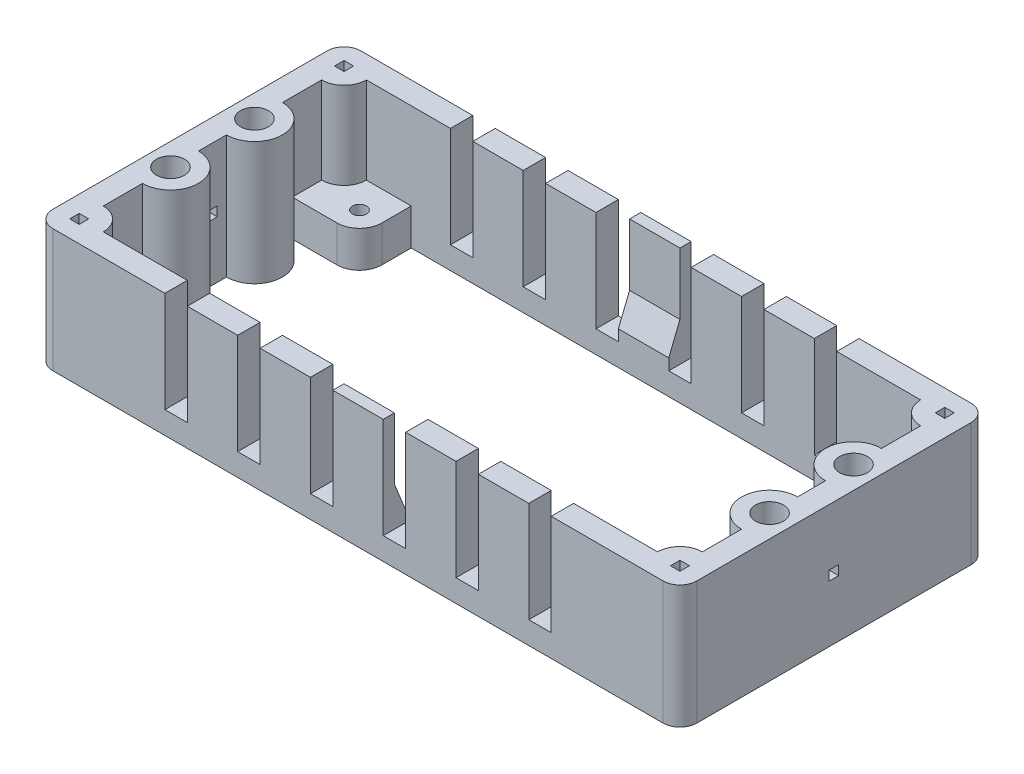
SolidWorks part; units mm, degrees
ref_plane "Спереди" through (0, 0, 0) normal (0, 0, 1) x (1, 0, 0)
ref_plane "Сверху" through (0, 0, 0) normal (0, 1, 0) x (1, 0, 0)
ref_plane "Справа" through (0, 0, 0) normal (1, 0, 0) x (0, 0, -1)
sketch "Эскиз1" plane through (0, 0, 0) normal (0, 1, 0) x (1, 0, 0)
  line L0 (-52.3285, 26.5877) -> (-52.3285, 15.5877)
  line L1 (-53.3285, 30.5877) -> (55.6715, 30.5877)
  line L2 (-56.3285, 27.5877) -> (-56.3285, -21.4123)
  line L3 (-53.3285, -24.4123) -> (55.6715, -24.4123)
  line L4 (58.6715, 27.5877) -> (58.6715, -21.4123)
  line L5 (-52.3285, 26.5877) -> (54.6715, 26.5877)
  line L7 (-52.3285, -20.4123) -> (54.6715, -20.4123)
  line L9 (-52.3285, 5.5877) -> (-52.3285, 0.5877)
  line L10 (-52.3285, -9.4123) -> (-52.3285, -20.4123)
  line L11 (54.6715, 15.5877) -> (54.6715, 26.5877)
  line L12 (54.6715, 5.5877) -> (54.6715, 0.5877)
  line L13 (54.6715, -9.4123) -> (54.6715, -20.4123)
  arc A0 (55.6715, -24.4123) -> (58.6715, -21.4123) centre (55.6715, -21.4123) ccw
  arc A1 (55.6715, 30.5877) -> (58.6715, 27.5877) centre (55.6715, 27.5877) cw
  arc A2 (-56.3285, -21.4123) -> (-53.3285, -24.4123) centre (-53.3285, -21.4123) ccw
  arc A3 (-53.3285, 30.5877) -> (-56.3285, 27.5877) centre (-53.3285, 27.5877) ccw
  arc A4 (-52.3285, 15.5877) -> (-52.3285, 5.5877) centre (-52.3285, 10.5877) cw
  arc A5 (-52.3285, 0.5877) -> (-52.3285, -9.4123) centre (-52.3285, -4.4123) cw
  arc A6 (54.6715, 15.5877) -> (54.6715, 5.5877) centre (54.6715, 10.5877) ccw
  arc A7 (54.6715, -9.4123) -> (54.6715, 0.5877) centre (54.6715, -4.4123) cw
  dimension "D3" = 3
  dimension "D8" = 5
  dimension "D9" = 5
  dimension "D1" = 115
  dimension "D2" = 55
  dimension "D4" = 4
  dimension "D6" = 4
  dimension "D10" = 15
  dimension "D11" = 16
  dimension "D12" = 15
  dimension "D13" = 16
extrude "Бобышка-Вытянуть1" add sketch "Эскиз1" along normal blind 22
sketch "Эскиз4" plane through (0, 0, 20.4123) normal (0, 0, -1) x (-1, 0, 0)
  line L1 (52.3285, 6.5) -> (40.3285, 6.5)
  line L2 (52.3285, 6.5) -> (52.3285, 0)
  line L3 (52.3285, 0) -> (40.3285, 0)
  line L4 (40.3285, 6.5) -> (40.3285, 0)
  line L5 (52.3285, 0) -> (-54.6715, 0) construction
  line L7 (-54.6715, 6.5) -> (-42.6715, 6.5)
  line L8 (-54.6715, 6.5) -> (-54.6715, 0)
  line L9 (-54.6715, 0) -> (-42.6715, 0)
  line L10 (-42.6715, 6.5) -> (-42.6715, 0)
  line L11 (-54.6715, 22) -> (-54.6715, 0) construction
  dimension "D1" = 6.5
  dimension "D2" = 6.5
  dimension "D3" = 12
  dimension "D4" = 12
  dimension "D5" = 0
extrude "Бобышка-Вытянуть3" add sketch "Эскиз4" along normal blind 9.25
fillet "Скругление1" radius 4 2 edges at (-40.3285, 3.25, 11.1623) (42.6715, 3.25, 11.1623)
sketch "Эскиз5" plane through (0, 0, -26.5877) normal (0, 0, 1) x (1, 0, 0)
  line L0 (54.6715, 22) -> (54.6715, 0) construction
  line L1 (-52.3285, 0) -> (-40.3285, 0)
  line L2 (-52.3285, 0) -> (-52.3285, 6.5)
  line L3 (-52.3285, 6.5) -> (-40.3285, 6.5)
  line L4 (-40.3285, 0) -> (-40.3285, 6.5)
  line L5 (54.6715, 0) -> (42.6715, 0)
  line L6 (54.6715, 0) -> (54.6715, 6.5)
  line L7 (54.6715, 6.5) -> (42.6715, 6.5)
  line L8 (42.6715, 0) -> (42.6715, 6.5)
  dimension "D1" = 12
  dimension "D2" = 12
  dimension "D3" = 6.5
  dimension "D4" = 6.5
  dimension "D5" = 0
extrude "Бобышка-Вытянуть4" add sketch "Эскиз5" along normal blind 9.25
fillet "Скругление2" radius 4 2 edges at (42.6715, 3.25, -17.3377) (-40.3285, 3.25, -17.3377)
sketch "Эскиз6" plane through (0, 22, 0) normal (0, 1, 0) x (1, 0, 0)
  circle A0 centre (-52.3285, 10.5877) radius 2.5
  circle A1 centre (-52.3285, -4.4123) radius 2.5
  circle A2 centre (54.6715, 10.5877) radius 2.5
  circle A3 centre (54.6715, -4.4123) radius 2.5
  dimension "D1" = 5
  dimension "D2" = 5
  dimension "D3" = 5
  dimension "D4" = 5
extrude "Вырез-Вытянуть1" cut sketch "Эскиз6" against normal blind 20
sketch "Эскиз7" plane through (0, 6.5, 0) normal (0, 1, 0) x (1, 0, 0)
  line L0 (-40.3285, 26.5877) -> (-52.3285, 26.5877) construction
  line L1 (-52.3285, 17.3377) -> (-52.3285, 26.5877) construction
  line L2 (54.6715, 17.3377) -> (54.6715, 26.5877) construction
  line L3 (54.6715, -11.1623) -> (54.6715, -20.4123) construction
  circle A0 centre (-44.3285, 21.3377) radius 1.25
  circle A1 centre (46.6715, 21.3377) radius 1.25
  circle A2 centre (46.6715, -15.1623) radius 1.25
  circle A3 centre (-44.3285, -15.1623) radius 1.25
  dimension "D1" = 2.5
  dimension "D2" = 2.5
  dimension "D3" = 2.5
  dimension "D4" = 2.5
  dimension "D5" = 91
  dimension "D6" = 91
  dimension "D7" = 36.5
  dimension "D8" = 36.5
  dimension "D9" = 5.25
  dimension "D10" = 8
  dimension "D11" = 8
  dimension "D12" = 8
extrude "Вырез-Вытянуть2" cut sketch "Эскиз7" against normal blind 20
sketch "Эскиз8" plane through (0, 2, 0) normal (0, 1, 0) x (1, 0, 0)
  circle A0 centre (-52.3285, 10.5877) radius 1.25
  circle A1 centre (-52.3285, -4.4123) radius 1.25
  circle A2 centre (54.6715, 10.5877) radius 1.25
  circle A3 centre (54.6715, -4.4123) radius 1.25
  dimension "D1" = 2.5
  dimension "D2" = 2.5
  dimension "D3" = 2.5
  dimension "D4" = 2.5
extrude "Вырез-Вытянуть3" cut sketch "Эскиз8" against normal blind 20
sketch "Эскиз9" plane through (-56.3285, 0, 0) normal (-1, 0, 0) x (0, 0, 1)
  line L0 (-30.5877, 22) -> (-30.5877, 0) construction
  line L1 (-3.9377, 11.85) -> (-2.2377, 11.85)
  line L2 (-3.9377, 11.85) -> (-3.9377, 10.15)
  line L3 (-3.9377, 10.15) -> (-2.2377, 10.15)
  line L4 (-2.2377, 11.85) -> (-2.2377, 10.15)
  line L5 (-27.5877, 22) -> (21.4123, 22) construction
  point P4 (-2.2377, 11)
  point P5 (-3.9377, 11)
  dimension "D1" = 1.7
  dimension "D2" = 1.7
  dimension "D3" = 26.65
  dimension "D4" = 10.15
extrude "Вырез-Вытянуть4" cut sketch "Эскиз9" against normal blind 120
sketch "Эскиз10" plane through (0, 6.5, 0) normal (0, 1, 0) x (1, 0, 0)
  line L0 (-40.3285, 26.5877) -> (-52.3285, 26.5877) construction
  line L1 (-52.3285, 17.3377) -> (-52.3285, 26.5877) construction
  line L2 (54.6715, 26.5877) -> (42.6715, 26.5877) construction
  line L3 (54.6715, 17.3377) -> (54.6715, 26.5877) construction
  line L4 (-52.3285, -11.1623) -> (-52.3285, -20.4123) construction
  line L5 (-52.3285, -20.4123) -> (-40.3285, -20.4123) construction
  line L6 (54.6715, -11.1623) -> (54.6715, -20.4123) construction
  line L7 (42.6715, -20.4123) -> (54.6715, -20.4123) construction
  line L8 (-52.3285, 22.5877) -> (-52.3285, 26.5877)
  line L9 (-52.3285, 26.5877) -> (-48.3285, 26.5877)
  line L10 (-52.3285, -16.4123) -> (-52.3285, -20.4123)
  line L11 (-52.3285, -20.4123) -> (-48.3285, -20.4123)
  line L12 (54.6715, -16.4123) -> (54.6715, -20.4123)
  line L13 (54.6715, -20.4123) -> (50.6715, -20.4123)
  line L14 (54.6715, 22.5877) -> (54.6715, 26.5877)
  line L15 (54.6715, 26.5877) -> (50.6715, 26.5877)
  arc A0 (-48.3285, 26.5877) -> (-52.3285, 22.5877) centre (-52.3285, 26.5877) cw
  arc A1 (50.6715, 26.5877) -> (54.6715, 22.5877) centre (54.6715, 26.5877) ccw
  arc A2 (-52.3285, -16.4123) -> (-48.3285, -20.4123) centre (-52.3285, -20.4123) cw
  arc A3 (54.6715, -16.4123) -> (50.6715, -20.4123) centre (54.6715, -20.4123) ccw
  dimension "D1" = 4
  dimension "D2" = 4
  dimension "D3" = 4
  dimension "D4" = 4
extrude "Бобышка-Вытянуть5" add sketch "Эскиз10" along normal blind 15.5
sketch "Эскиз11" plane through (0, 22, 0) normal (0, 1, 0) x (1, 0, 0)
  line L0 (55.6715, 30.5877) -> (-53.3285, 30.5877) construction
  line L1 (-53.3285, 27.5877) -> (-51.6285, 27.5877)
  line L2 (-53.3285, 27.5877) -> (-53.3285, 25.8877)
  line L3 (-53.3285, 25.8877) -> (-51.6285, 25.8877)
  line L4 (-51.6285, 27.5877) -> (-51.6285, 25.8877)
  line L5 (-56.3285, 27.5877) -> (-56.3285, -21.4123) construction
  line L6 (58.6715, -21.4123) -> (58.6715, 27.5877) construction
  line L7 (53.9715, 27.5877) -> (55.6715, 27.5877)
  line L8 (53.9715, 27.5877) -> (53.9715, 25.8877)
  line L9 (53.9715, 25.8877) -> (55.6715, 25.8877)
  line L10 (55.6715, 27.5877) -> (55.6715, 25.8877)
  line L11 (-53.3285, -24.4123) -> (55.6715, -24.4123) construction
  line L12 (53.9715, -19.7123) -> (55.6715, -19.7123)
  line L13 (53.9715, -19.7123) -> (53.9715, -21.4123)
  line L14 (53.9715, -21.4123) -> (55.6715, -21.4123)
  line L15 (55.6715, -19.7123) -> (55.6715, -21.4123)
  line L17 (-53.3285, -19.7123) -> (-51.6285, -19.7123)
  line L18 (-53.3285, -19.7123) -> (-53.3285, -21.4123)
  line L19 (-53.3285, -21.4123) -> (-51.6285, -21.4123)
  line L20 (-51.6285, -19.7123) -> (-51.6285, -21.4123)
  point P18 (54.8215, -21.4123)
  point P19 (53.9715, -20.5623)
  point P26 (-52.4785, -21.4123)
  point P27 (-53.3285, -20.5623)
  dimension "D1" = 1.7
  dimension "D2" = 1.7
  dimension "D3" = 3
  dimension "D4" = 3
  dimension "D5" = 1.7
  dimension "D6" = 1.7
  dimension "D7" = 3
  dimension "D8" = 3
  dimension "D9" = 1.7
  dimension "D10" = 1.7
  dimension "D11" = 3
  dimension "D12" = 3
  dimension "D13" = 1.7
  dimension "D14" = 1.7
  dimension "D15" = 3
  dimension "D16" = 3
extrude "Вырез-Вытянуть5" cut sketch "Эскиз11" against normal blind 5
sketch "Эскиз12" plane through (0, 0, 24.4123) normal (0, 0, 1) x (1, 0, 0)
  line L0 (-53.3285, 22) -> (55.6715, 22) construction
  line L1 (-33.3285, 22) -> (-29.3285, 22)
  line L2 (-33.3285, 22) -> (-33.3285, 4)
  line L3 (-33.3285, 4) -> (-29.3285, 4)
  line L4 (-29.3285, 22) -> (-29.3285, 4)
  line L5 (-53.3285, 0) -> (55.6715, 0) construction
  line L6 (-56.3285, 22) -> (-56.3285, 0) construction
  line L7 (-20.3285, 22) -> (-16.3285, 22)
  line L8 (-20.3285, 22) -> (-20.3285, 4)
  line L9 (-20.3285, 4) -> (-16.3285, 4)
  line L10 (-16.3285, 22) -> (-16.3285, 4)
  line L11 (-7.3285, 22) -> (-3.3285, 22)
  line L12 (-7.3285, 22) -> (-7.3285, 4)
  line L13 (-7.3285, 4) -> (-3.3285, 4)
  line L14 (-3.3285, 22) -> (-3.3285, 4)
  line L15 (5.6715, 22) -> (9.6715, 22)
  line L16 (5.6715, 22) -> (5.6715, 4)
  line L17 (5.6715, 4) -> (9.6715, 4)
  line L18 (9.6715, 22) -> (9.6715, 4)
  line L19 (18.6715, 22) -> (22.6715, 22)
  line L20 (18.6715, 22) -> (18.6715, 4)
  line L21 (18.6715, 4) -> (22.6715, 4)
  line L22 (22.6715, 22) -> (22.6715, 4)
  line L23 (35.6715, 22) -> (31.6715, 22)
  line L24 (35.6715, 22) -> (35.6715, 4)
  line L25 (35.6715, 4) -> (31.6715, 4)
  line L26 (31.6715, 22) -> (31.6715, 4)
  point P28 (-3.3285, 13)
  dimension "D1" = 4
  dimension "D2" = 4
  dimension "D3" = 4
  dimension "D4" = 4
  dimension "D5" = 4
  dimension "D6" = 4
  dimension "D7" = 4
  dimension "D8" = 9
  dimension "D9" = 9
  dimension "D10" = 9
  dimension "D11" = 9
  dimension "D12" = 9
  dimension "D13" = 23
extrude "Вырез-Вытянуть6" cut sketch "Эскиз12" against normal blind 71
sketch "Эскиз13" plane through (0, 22, 0) normal (0, 1, 0) x (1, 0, 0)
  line L0 (-3.3285, 30.5877) -> (-3.3285, 26.5877) construction
  line L1 (-3.3285, 28.5877) -> (5.6715, 28.5877)
  line L2 (-3.3285, 28.5877) -> (-3.3285, 26.5877)
  line L3 (-3.3285, 26.5877) -> (5.6715, 26.5877)
  line L4 (5.6715, 28.5877) -> (5.6715, 26.5877)
  line L5 (5.6715, 30.5877) -> (5.6715, 26.5877) construction
  line L6 (-3.3285, -20.4123) -> (-3.3285, -24.4123) construction
  line L7 (5.6715, -20.4123) -> (-3.3285, -20.4123)
  line L8 (5.6715, -20.4123) -> (5.6715, -22.4123)
  line L9 (5.6715, -22.4123) -> (-3.3285, -22.4123)
  line L10 (-3.3285, -20.4123) -> (-3.3285, -22.4123)
extrude "Вырез-Вытянуть7" cut sketch "Эскиз13" against normal blind 11
chamfer "Фаска1" distance 5 angle 22 2 edges at (1.1715, 11, -26.5877) (1.1715, 11, 20.4123) first distance on face at (1.1715, 11.25, -26.5877) first distance on face at (1.1715, 11.25, 20.4123)
